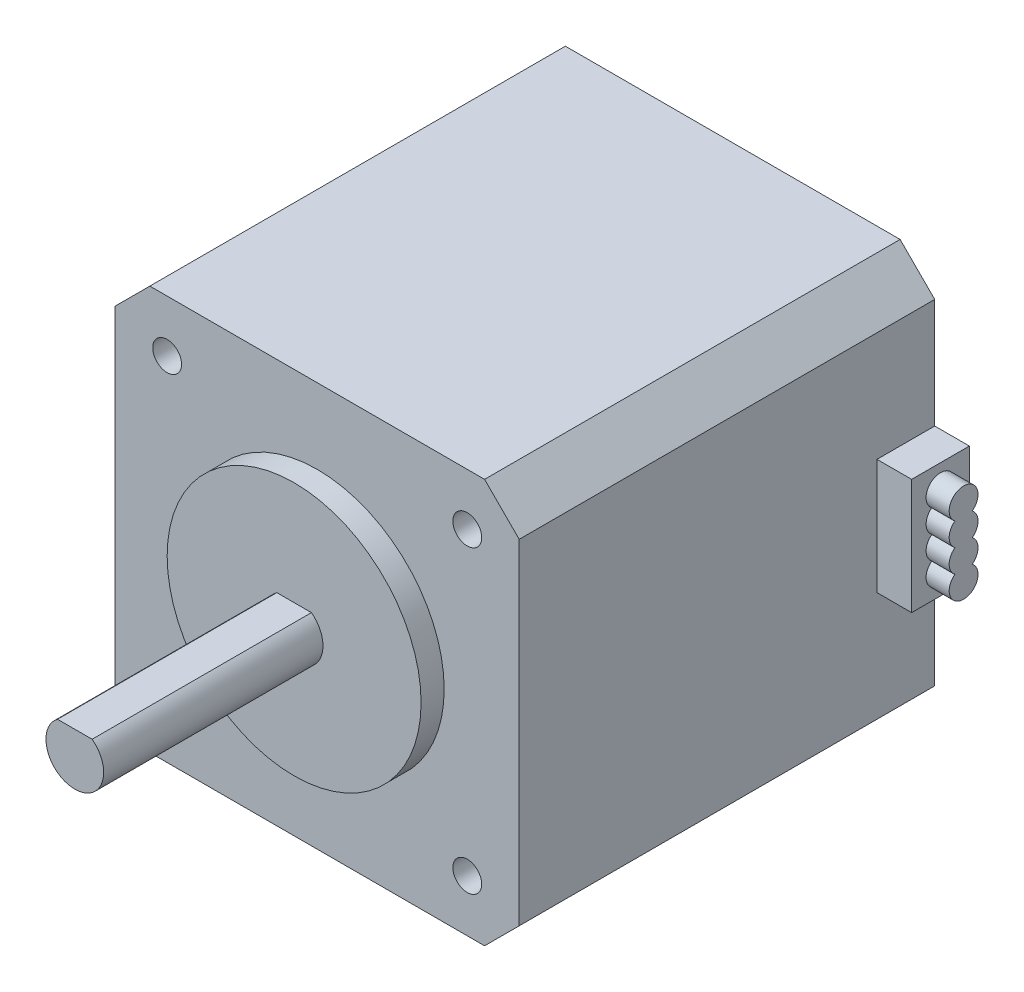
SolidWorks part; units mm, degrees
ref_plane "Front Plane" through (0, 0, 0) normal (0, 0, 1) x (1, 0, 0)
ref_plane "Top Plane" through (0, 0, 0) normal (0, 1, 0) x (1, 0, 0)
ref_plane "Right Plane" through (0, 0, 0) normal (1, 0, 0) x (0, 0, -1)
sketch "Sketch1" plane through (0, 0, 0) normal (0, 0, 1) x (1, 0, 0)
  line L0 (-14.5, 17.5) -> (-17.5, 14.5)
  line L1 (14.5, -17.5) -> (-14.5, -17.5)
  line L2 (17.5, -14.5) -> (17.5, 14.5)
  line L3 (14.5, 17.5) -> (-14.5, 17.5)
  line L4 (-17.5, -14.5) -> (-17.5, 14.5)
  line L5 (17.5, -17.5) -> (-17.5, 17.5) construction
  line L6 (17.5, 17.5) -> (-17.5, -17.5) construction
  line L7 (17.5, 14.5) -> (14.5, 17.5)
  line L8 (17.5, -14.5) -> (14.5, -17.5)
  line L9 (-14.5, -17.5) -> (-17.5, -14.5)
  line L10 (-1.5, 2) -> (1.5, 2)
  arc A0 (-1.5, 2) -> (1.5, 2) centre (0, 0) ccw
  circle A1 centre (0, 0) radius 11
  arc A2 (-1.5, 2) -> (1.5, 2) centre (0, 0) cw construction
  point P0 (0, 0)
  point P6 (-13, 13)
  point P12 (13, 13)
  point P13 (13, -13)
  point P14 (-13, -13)
  point P15 (0, 0)
  point P24 (0, 2.5)
  dimension "D2" = 22
  dimension "D3" = 4
  dimension "D5" = 5
  dimension "D1" = 35
  dimension "D4" = 26
  dimension "D6" = 0.5
extrude "Boss-Extrude1" add sketch "Sketch1" against normal blind 36 contours L3 L0 L4 L9 L1 L8 L2 L7
extrude "Boss-Extrude2" add sketch "Sketch1<3>" along normal blind 2 contours A1
sketch "Sketch1<3>" plane through (0, 0, 0) normal (0, 0, 1) x (1, 0, 0) same geometry as "Sketch1"
hole_wizard "M3x0.5 Tapped Hole1" positions "Sketch3" profile "Sketch2" tap size "M3x0.5" standard "ANSI Metric"
sketch "Sketch3" plane through (0, 0, 0) normal (0, 0, 1) x (1, 0, 0)
  point P0 (13, 13)
  point P3 (-13, 13)
  point P6 (-13, -13)
  point P9 (13, -13)
sketch "Sketch2" plane through (13, 13, 0) normal (1, 0, 0) x (0, -1, 0)
  line L0 (0, 0) -> (0, 5.7511)
  line L1 (0, 5.7511) -> (1.25, 5)
  line L2 (1.25, 5) -> (1.25, 0)
  line L5 (1.25, 0) -> (0, 0)
  line L10 (0, 5.7511) -> (-1.25, 5) construction
  line L11 (0, -6.35) -> (0, 107.95) construction
  dimension "Tap Drill Dia." = 2.5
  dimension "Tap Drill Depth" = 5
  dimension "Drill Angle" = 118
cosmetic thread "Hole Thread1" parameters "D1"=4, "D2"=3
cosmetic thread "Hole Thread2" parameters "D1"=4, "D2"=3
cosmetic thread "Hole Thread3" parameters "D1"=4, "D2"=3
cosmetic thread "Hole Thread4" parameters "D1"=4, "D2"=3
extrude "Boss-Extrude3" add sketch "Sketch1<4>" along normal blind 21 contours L10 A0 region at (0, -0.1209, 0)
sketch "Sketch1<4>" plane through (0, 0, 0) normal (0, 0, 1) x (1, 0, 0) same geometry as "Sketch1"
sketch "Sketch4" plane through (17.5, 0, 0) normal (1, 0, 0) x (0, 0, -1)
  line L0 (36, -14.5) -> (36, 14.5) construction
  line L1 (31, -5) -> (36, -5)
  line L2 (31, -5) -> (31, 5)
  line L3 (31, 5) -> (36, 5)
  line L4 (36, -5) -> (36, 5)
  line L5 (31, -5) -> (36, 5) construction
  line L6 (31, 5) -> (36, -5) construction
  line L7 (36, 0) -> (0, 0) construction
  line L8 (33.5, -3) -> (33.5, -5)
  line L9 (33.5, -5) -> (40.1935, -8.3396)
  line L10 (40.1935, -8.3396) -> (40.258, -8.3073)
  line L11 (33.5, -3) -> (33.5, -1)
  line L12 (33.5, -1) -> (33.5, 1)
  line L13 (33.5, 1) -> (33.5, 3)
  line L14 (33.5, 3) -> (33.5, 5)
  circle A0 centre (33.5, 3) radius 1.25
  circle A1 centre (33.5, 1) radius 1.25
  circle A2 centre (33.5, -1) radius 1.25
  circle A3 centre (33.5, -3) radius 1.25
  point P0 (33.5, 0)
  dimension "D3" = 2.5
  dimension "D1" = 10
  dimension "D2" = 5
extrude "Boss-Extrude4" add sketch "Sketch4" along normal blind 3 contours L3 L4 L1 L2
extrude "Boss-Extrude5" add sketch "Sketch4<3>" along normal blind 2 from surface contours A0 | A1 | A2 | A3 starting at face at (20.5, 0, -33.5)
sketch "Sketch4<3>" plane through (17.5, 0, 0) normal (1, 0, 0) x (0, 0, -1) same geometry as "Sketch4"
